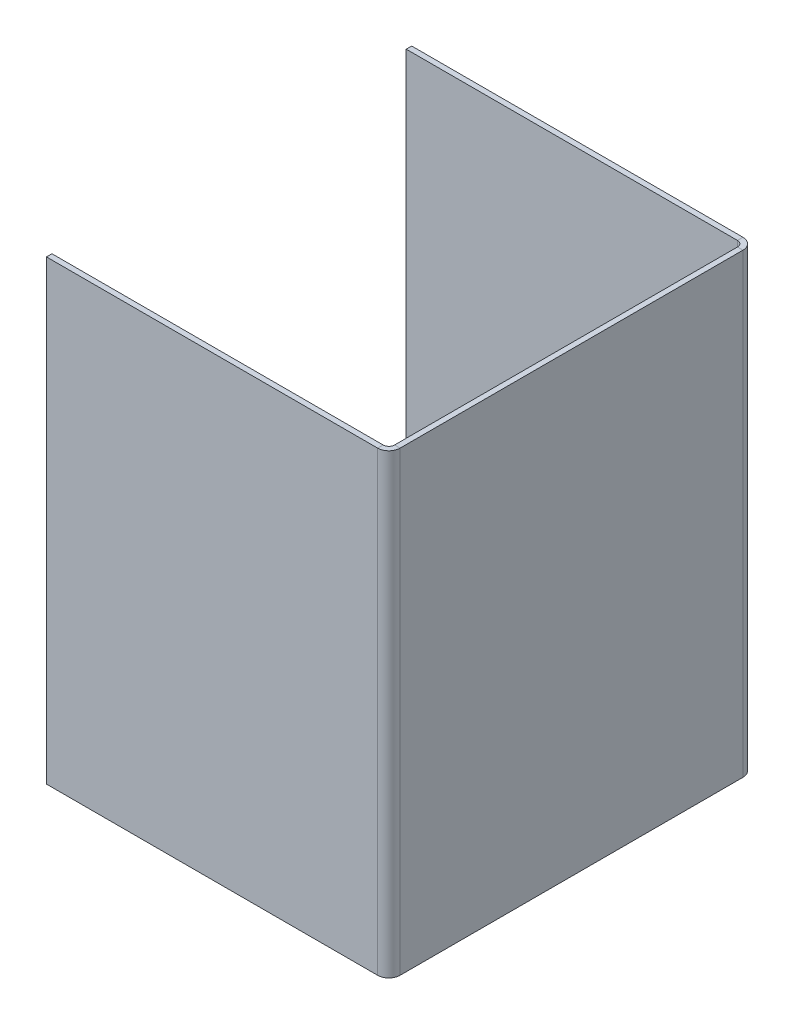
SolidWorks part; units mm, degrees
note: The reader was unsure of these and kept them because the rebuilt part matched: thickness of "Base-Flange1", "Edge-Flange1", "Edge-Flange2", "Sheet-Metal1", "Sheet-Metal2", "Sheet-Metal3"; flange length of "Edge-Flange1", "Edge-Flange2".
ref_plane "Front Plane" through (0, 0, 0) normal (0, 0, 1) x (1, 0, 0)
ref_plane "Top Plane" through (0, 0, 0) normal (0, 1, 0) x (1, 0, 0)
ref_plane "Right Plane" through (0, 0, 0) normal (1, 0, 0) x (0, 0, -1)
sketch "Sketch1" plane through (0, 0, 0) normal (1, 0, 0) x (0, 0, -1)
  line L1 (0, 0) -> (81.28, 0)
  line L2 (0, 0) -> (0, 101.6)
  line L3 (0, 101.6) -> (81.28, 101.6)
  line L4 (81.28, 0) -> (81.28, 101.6)
  dimension "D1" = 101.6
  dimension "D2" = 81.28
base flange "Base-Flange1" sketch "Sketch1" thickness 1.2192 reverse thickness direction no parameters "D1"=1.27
edge flange "Edge-Flange1" sketch "Sketch8" flange angle 90 flange length 76.2 flange position material inside bend radius 1.27 thickness 1.2192 relief rectangular parameters "D6"=10
sketch "Sketch8" plane through (-1.2192, 0, 0) normal (0, 0, -1) x (0, -1, 0)
  line L2 (-101.6, 0) -> (-101.6, 74.9808)
  line L3 (-101.6, 74.9808) -> (0, 74.9808)
  line L4 (0, 74.9808) -> (0, 0)
  line L5 (0, 0) -> (-101.6, 0) construction
  line L6 (0, 0) -> (-101.6, 0)
bend "EdgeBend1" bend radius 1.27 bend angle 90 parameters "D5"=1
edge flange "Edge-Flange2" sketch "Sketch11" flange angle 90 flange length 76.2 flange position material inside bend radius 1.27 thickness 1.2192 relief rectangular parameters "D6"=10
sketch "Sketch11" plane through (-1.2192, 0, -81.28) normal (0, 0, -1) x (0, -1, 0)
  line L0 (0, 0) -> (-101.6, 0) construction
  line L1 (0, 0) -> (-101.6, 0)
  line L2 (-101.6, 0) -> (-101.6, 74.9808)
  line L3 (-101.6, 74.9808) -> (0, 74.9808)
  line L4 (0, 74.9808) -> (0, 0)
bend "EdgeBend2" bend radius 1.27 bend angle 90 parameters "D5"=2
sketch "Bend-Lines1" [suppressed] plane through (0, 0, 0) normal (0, 1, 0) x (1, 0, 0)
sketch "Bounding-Box1" [suppressed] plane through (0, 0, 0) normal (0, 1, 0) x (1, 0, 0)
sheet metal parameters "Sheet-Metal1" thickness 1.2192 parameters "D1"=1.27
flat pattern "Flat-Pattern1" [suppressed]
sketch "Bend-Lines2" plane through (0, 0, 0) normal (0, 1, 0) x (1, 0, 0)
sketch3d "Bounding-Box2" [suppressed]
  line L0 (0, 101.6, 0) -> (0, 0, 0) construction
  line L1 (-76.2, 101.6, 0) -> (-76.2, 0, 0) construction
  line L2 (0, 101.6, 0) -> (-76.2, 101.6, 0) construction
  line L3 (0, 0, 0) -> (-76.2, 0, 0) construction
sheet metal parameters "Sheet-Metal2" thickness 1.2192 parameters "D1"=1.27, "D7"=0.889
flat pattern "Flat-Pattern1"
sketch "Bend-Lines2" plane through (0, 0, 0) normal (1, 0, 0) x (0, 0, -1)
  line L0 (0.8124, 101.6) -> (0.8124, 0) construction
  line L1 (0.8124, 101.6) -> (0.8124, 0) construction
sketch3d "Bounding-Box2" [suppressed]
  line L0 (76.2, 0, 0) -> (-99.9751, 0, 0) construction
  line L1 (76.2, 101.6, 0) -> (-99.9751, 101.6, 0) construction
  line L2 (76.2, 0, 0) -> (76.2, 101.6, 0) construction
  line L3 (-99.9751, 0, 0) -> (-99.9751, 101.6, 0) construction
bend of the flat pattern "Flatten-<EdgeBend1>1"
sheet metal parameters "Sheet-Metal3" thickness 1.2192 parameters "D1"=1.27, "D7"=0.889
flat pattern "Flat-Pattern1"
sketch "Bend-Lines2" plane through (0, 0, 0) normal (1, 0, 0) x (0, 0, -1)
  line L0 (1.013, 101.6) -> (1.013, 0) construction
  line L1 (1.013, 101.6) -> (1.013, 0) construction
  line L2 (80.267, 0) -> (80.267, 101.6) construction
  line L3 (80.267, 0) -> (80.267, 101.6) construction
sketch3d "Bounding-Box2" [suppressed]
  line L0 (155.4541, 0, 0) -> (-74.1741, 0, 0) construction
  line L1 (155.4541, 101.6, 0) -> (-74.1741, 101.6, 0) construction
  line L2 (155.4541, 0, 0) -> (155.4541, 101.6, 0) construction
  line L3 (-74.1741, 0, 0) -> (-74.1741, 101.6, 0) construction
bend of the flat pattern "Flatten-<EdgeBend1>1"
bend of the flat pattern "Flatten-<EdgeBend2>1"
